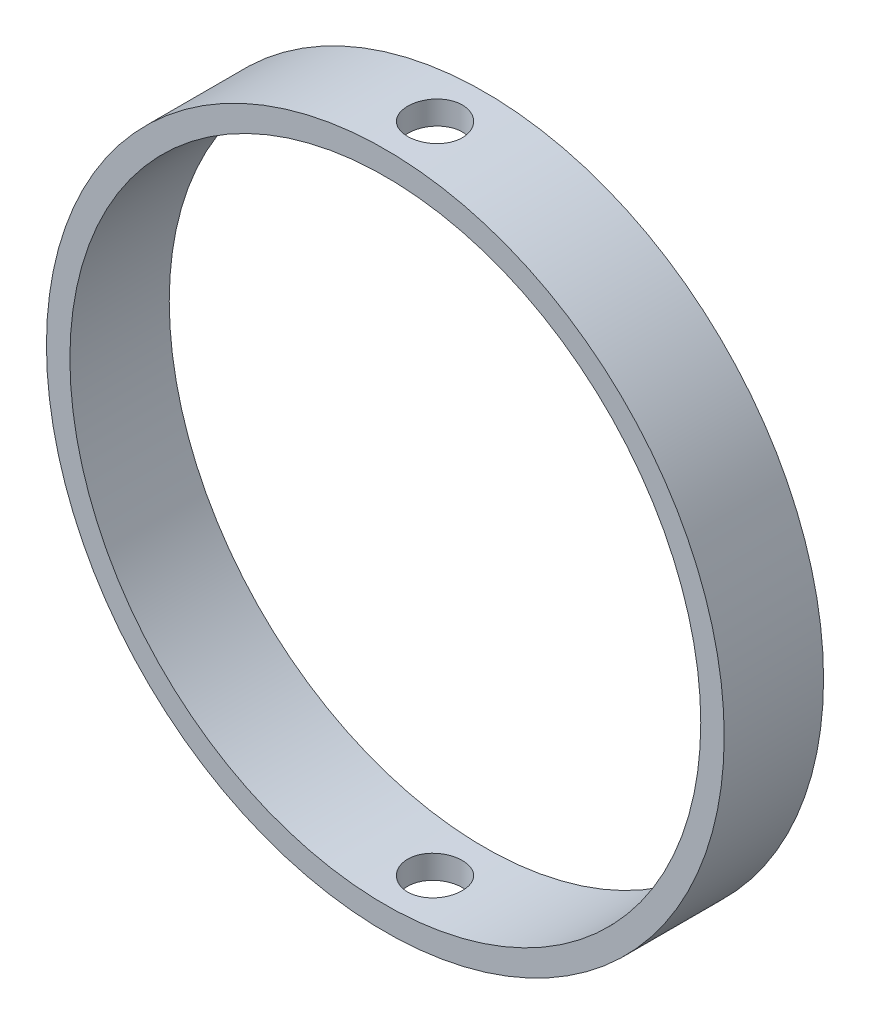
SolidWorks part; units mm, degrees
ref_plane "Front Plane" through (0, 0, 0) normal (0, 0, 1) x (1, 0, 0)
ref_plane "Top Plane" through (0, 0, 0) normal (0, 1, 0) x (1, 0, 0)
ref_plane "Right Plane" through (0, 0, 0) normal (1, 0, 0) x (0, 0, -1)
sketch "Sketch1" plane through (0, 0, 0) normal (0, 0, 1) x (1, 0, 0)
  circle A0 centre (0, 0) radius 34.11
  circle A1 centre (0, 0) radius 31.75
  dimension "D1" = 68.22
  dimension "D2" = 63.5
extrude "Boss-Extrude1" add sketch "Sketch1" along normal blind 10
ref_plane "Plane1" through (0, 34.11, 0) normal (0, 1, 0) x (1, 0, 0)
sketch "Sketch2" plane through (0, 34.11, 0) normal (0, 1, 0) x (1, 0, 0)
  circle A0 centre (0, -5) radius 2.75
  dimension "D1" = 5.5
  dimension "D2" = 5
extrude "Cut-Extrude1" cut sketch "Sketch2" against normal through all
